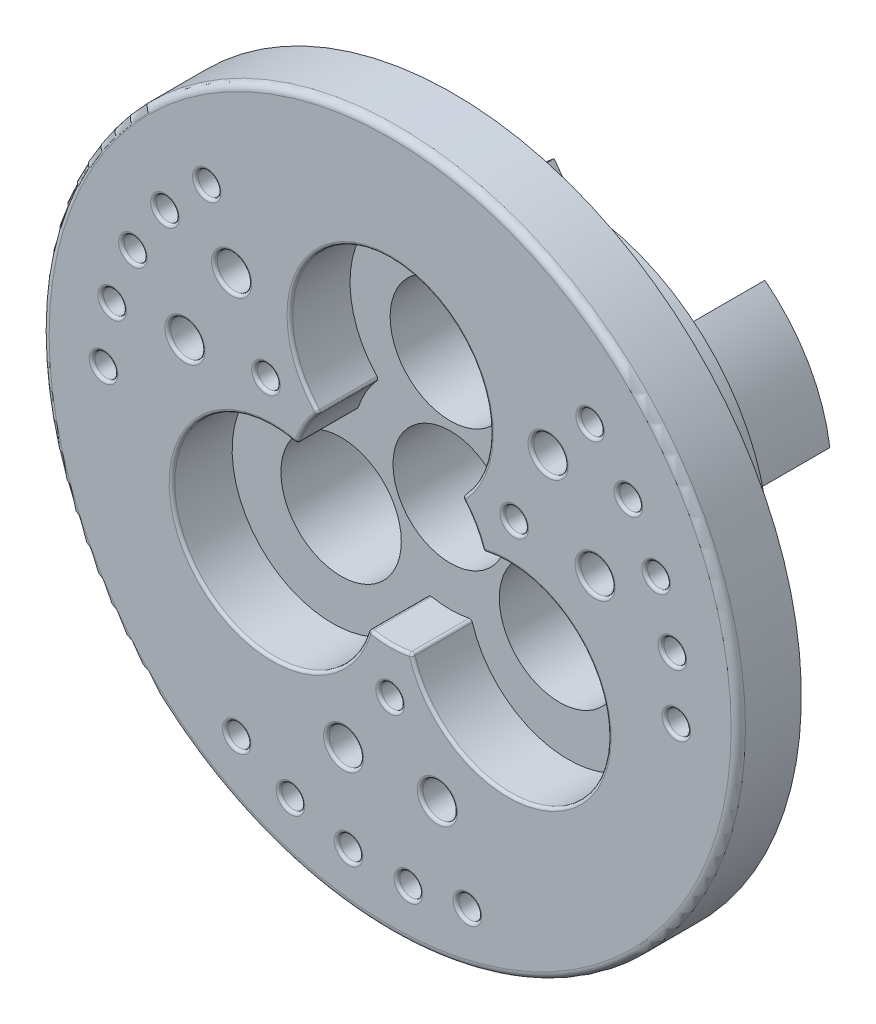
SolidWorks part; units mm, degrees
ref_plane "Plan de face" through (0, 0, 0) normal (0, 0, 1) x (1, 0, 0)
ref_plane "Plan de dessus" through (0, 0, 0) normal (0, 1, 0) x (1, 0, 0)
ref_plane "Plan de droite" through (0, 0, 0) normal (1, 0, 0) x (0, 0, -1)
sketch "Esquisse1" plane through (0, 0, 0) normal (1, 0, 0) x (0, 0, -1)
  line L0 (0, 20) -> (0, 70)
  line L1 (0, 70) -> (-40, 70)
  line L2 (-40, 70) -> (-40, 121.5)
  line L3 (-40, 121.5) -> (-62, 121.5)
  line L4 (-62, 121.5) -> (-62, 20)
  line L5 (-62, 20) -> (0, 20)
  line L6 (0, 0) -> (-218.9749, 0) construction
  dimension "D1" = 20
  dimension "D2" = 121.5
  dimension "D3" = 70
  dimension "D4" = 62
  dimension "D5" = 40
revolve "Révolution1" add sketch "Esquisse1" angle 360 about L6
sketch "Esquisse3" plane through (0, 0, 0) normal (0, 0, -1) x (-1, 0, 0)
  line L0 (0, 0) -> (0, 114.8369) construction
  line L1 (0, 0) -> (130.9393, 0) construction
  line L2 (0, 0) -> (103.8356, 59.9495) construction
  line L3 (59.4433, 8.1546) -> (27.5844, 4.8061)
  line L4 (17.9544, 21.4858) -> (36.7837, 47.4021)
  line L5 (9.63, -26.2919) -> (22.6595, -55.5567)
  line L6 (-22.6595, -55.5567) -> (-9.63, -26.2919)
  line L7 (-27.5844, 4.8061) -> (-59.4433, 8.1546)
  line L8 (-36.7837, 47.4021) -> (-17.9544, 21.4858)
  line L9 (0, 0) -> (27.5844, 4.8061) construction
  line L10 (0, 0) -> (0, 44) construction
  circle A0 centre (0, 44) radius 21
  arc A3 (27.5844, 4.8061) -> (17.9544, 21.4858) centre (0, 0) ccw
  arc A4 (59.4433, 8.1546) -> (36.7837, 47.4021) centre (0, 0) ccw
  arc A5 (-22.6595, -55.5567) -> (22.6595, -55.5567) centre (0, 0) ccw
  arc A6 (-9.63, -26.2919) -> (9.63, -26.2919) centre (0, 0) ccw
  arc A7 (-36.7837, 47.4021) -> (-59.4433, 8.1546) centre (0, 0) ccw
  arc A8 (-17.9544, 21.4858) -> (-27.5844, 4.8061) centre (0, 0) ccw
  circle A9 centre (38.1051, -22) radius 21
  circle A10 centre (-38.1051, -22) radius 21
  dimension "D2" = 42
  dimension "D4" = 3
  dimension "D1" = 30
  dimension "D3" = 44
  dimension "D5" = 28
  dimension "D6" = 24
  dimension "D7" = 24
  dimension "D9" = 44
  dimension "D8" = 3
extrude "Enlèv. mat.-Extru.1" cut sketch "Esquisse3" against normal offset from surface 20 and the other way through all contours A0 | A10 | A9 region at (0, 44, 0) region at (-38.1051, -22, 0) region at (38.1051, -22, 0) up to face at (-20, 0, 62)
extrude "Boss.-Extru.1" add sketch "Esquisse3<3>" along normal blind 32 contours A8 L8 A7 L7 | L3 A4 L4 A3 | A6 L6 A5 L5 region at (-39.0329, 22.5357, 0) region at (0, -45.0713, 0) region at (39.0329, 22.5357, 0)
sketch "Esquisse3<3>" plane through (0, 0, 0) normal (0, 0, -1) x (-1, 0, 0) same geometry as "Esquisse3"
sketch "Esquisse5" plane through (0, 0, 62) normal (0, 0, 1) x (1, 0, 0)
  line L0 (0, 0) -> (0, 47.5) construction
  circle A0 centre (0, 0) radius 47.5 construction
  arc A1 (25.0182, 23.0237) -> (-25.0182, 23.0237) centre (0, 47.5) ccw
  arc A2 (7.43, -33.1782) -> (32.4482, 10.1545) centre (41.1362, -23.75) ccw
  arc A3 (-32.4482, 10.1545) -> (-7.43, -33.1782) centre (-41.1362, -23.75) ccw
  arc A7 (-7.43, -33.1782) -> (7.43, -33.1782) centre (0, 0) ccw
  arc A8 (-25.0182, 23.0237) -> (-32.4482, 10.1545) centre (0, 0) ccw
  arc A9 (32.4482, 10.1545) -> (25.0182, 23.0237) centre (0, 0) ccw
  dimension "D1" = 95
  dimension "D2" = 70
  dimension "D4" = 68
  dimension "D3" = 3
extrude "Enlèv. mat.-Extru.2" cut sketch "Esquisse5" against normal blind 21
fillet "Congé1" radius 2.5 1 edges at (-121.5, 0, 62)
fillet "Congé2" radius 1 12 edges at (-7.43, -33.1782, 51.5) (7.43, -33.1782, 51.5) (32.4482, 10.1545, 51.5) (25.0182, 23.0237, 51.5) (-25.0182, 23.0237, 51.5) (-32.4482, 10.1545, 51.5) (-29.4449, 17, 62) (0, 82.5, 62) (29.4449, 17, 62) (71.4471, -41.25, 62) (0, -34, 62) (-71.4471, -41.25, 62)
sketch "Esquisse6" plane through (0, 0, -32) normal (0, 0, -1) x (-1, 0, 0)
  line L1 (0, 0) -> (-43.3013, 25) construction
  line L2 (-36.7837, 47.4021) -> (-17.9544, 21.4858) construction
  line L3 (-27.5776, 23.1404) -> (0, 0) construction
  line L4 (-36.7837, 47.4021) -> (-17.9544, 21.4858) construction
  line L5 (-33.8289, 12.3127) -> (0, 0) construction
  line L6 (-27.5844, 4.8061) -> (-59.4433, 8.1546) construction
  line L7 (0, 0) -> (-27.5776, 23.1404) construction
  circle A0 centre (-43.3013, 25) radius 6
  circle A1 centre (-33.8289, 12.3127) radius 4
  circle A2 centre (-27.5776, 23.1404) radius 4
  circle A3 centre (0, 0) radius 36 construction
  circle A4 centre (0, 0) radius 50 construction
  circle A5 centre (33.8289, 12.3127) radius 4
  circle A6 centre (27.5776, 23.1404) radius 4
  circle A7 centre (43.3013, 25) radius 6
  circle A8 centre (-6.2513, -35.4531) radius 4
  circle A9 centre (6.2513, -35.4531) radius 4
  circle A10 centre (0, -50) radius 6
  dimension "D1" = 12
  dimension "D2" = 8
  dimension "D3" = 8
  dimension "D5" = 72
  dimension "D6" = 100
  dimension "D4" = 14
  dimension "D7" = 24
  dimension "D8" = 14
  dimension "D10" = 36
  dimension "D9" = 3
hole_wizard "Trous de centrage Ø8.0mm1" positions "Esquisse7" profile "Esquisse8" hole size "Ø8.0" standard "ISO"
sketch "Esquisse7" plane through (0, 0, -32) normal (0, 0, -1) x (-1, 0, 0)
  point P0 (-27.5776, 23.1404)
  point P3 (-33.8289, 12.3127)
  point P7 (33.8289, 12.3127)
  point P10 (27.5776, 23.1404)
  point P13 (6.2513, -35.4531)
  point P16 (-6.2513, -35.4531)
sketch "Esquisse8" plane through (27.5776, 23.1404, -32) normal (1, 0, 0) x (0, 1, 0)
  line L0 (0, 0) -> (0, 24.4034)
  line L1 (0, 24.4034) -> (4, 22)
  line L2 (4, 22) -> (4, 0)
  line L5 (4, 0) -> (0, 0)
  line L10 (0, 24.4034) -> (-4, 22) construction
  line L11 (0, -6.35) -> (0, 107.95) construction
  dimension "Diamètre du perçage" = 8
  dimension "Profondeur du perçage" = 22
  dimension "Angle de pointe" = 118
hole_wizard "Dégagement M121" positions "Esquisse3D1" profile "Esquisse9" hole size "M12" standard "ISO"
sketch3d "Esquisse3D1"
  point P0 (43.3013, 25, -32)
  point P3 (0, -50, -32)
  point P6 (-43.3013, 25, -32)
sketch "Esquisse9" plane through (43.3013, 25, -32) normal (1, 0, 0) x (0, 1, 0)
  line L0 (0, 0) -> (0, 31.9056)
  line L1 (0, 31.9056) -> (6.5, 28)
  line L2 (6.5, 28) -> (6.5, 0)
  line L5 (6.5, 0) -> (0, 0)
  line L10 (0, 31.9056) -> (-6.5, 28) construction
  line L11 (0, -6.35) -> (0, 107.95) construction
  dimension "Diamètre du perçage" = 13
  dimension "Profondeur du perçage" = 28
  dimension "Angle de pointe" = 118
sketch "Esquisse10" plane through (0, 0, 62) normal (0, 0, 1) x (1, 0, 0)
  line L0 (-0.0806, -4.0148) -> (-100.0174, 0) construction
  line L1 (-55.2958, 50.6693) -> (0, 0) construction
  line L2 (0, 0) -> (-100.0174, 0) construction
  line L3 (0, 0) -> (-71.6069, 22.3038) construction
  line L4 (0, 0) -> (-55.2958, 50.6693) construction
  circle A0 centre (0, 0) radius 100.0174 construction
  circle A1 centre (-100.0174, 0) radius 4
  circle A5 centre (-96.9988, 20.6903) radius 4
  circle A6 centre (-89.7444, 40.3008) radius 4
  circle A7 centre (-78.5713, 57.9746) radius 4
  circle A8 centre (-63.9678, 72.9391) radius 4
  circle A9 centre (-46.5721, 84.5404) radius 4 [skipped]
  circle A10 centre (-27.1444, 92.2713) radius 4 [skipped]
  circle A11 centre (-6.534, 95.7941) radius 4 [skipped]
  circle A12 centre (14.3584, 94.9548) radius 4 [skipped]
  circle A13 centre (34.6199, 89.79) radius 4 [skipped]
  circle A14 centre (53.3647, 80.5255) radius 4 [skipped]
  circle A15 centre (69.7737, 67.5662) radius 4
  circle A16 centre (83.1298, 51.4785) radius 4
  circle A17 centre (92.8491, 32.9654) radius 4
  circle A18 centre (98.507, 12.8361) radius 4
  circle A19 centre (99.8561, -8.0296) radius 4
  circle A20 centre (96.8376, -28.7199) radius 4 [skipped]
  circle A21 centre (89.5832, -48.3305) radius 4 [skipped]
  circle A22 centre (78.4101, -66.0042) radius 4 [skipped]
  circle A23 centre (63.8065, -80.9687) radius 4 [skipped]
  circle A24 centre (46.4108, -92.57) radius 4 [skipped]
  circle A25 centre (26.9832, -100.301) radius 4
  circle A26 centre (6.3728, -103.8238) radius 4
  circle A27 centre (-14.5197, -102.9844) radius 4
  circle A28 centre (-34.7811, -97.8197) radius 4
  circle A29 centre (-53.5259, -88.5552) radius 4
  circle A30 centre (-69.9349, -75.5959) radius 4 [skipped]
  circle A31 centre (-83.291, -59.5081) radius 4 [skipped]
  circle A32 centre (-93.0104, -40.995) radius 4 [skipped]
  circle A33 centre (-98.6682, -20.8658) radius 4 [skipped]
  circle A34 centre (0, -50) radius 4
  circle A35 centre (43.3013, 25) radius 4
  circle A36 centre (-43.3013, 25) radius 4
  circle A37 centre (0, 0) radius 75 construction
  circle A38 centre (-71.6069, 22.3038) radius 6
  circle A39 centre (-55.2958, 50.6693) radius 6
  circle A40 centre (71.5288, 22.5529) radius 6
  circle A41 centre (55.1191, 50.8615) radius 6
  circle A42 centre (-16.233, -73.2222) radius 6
  circle A43 centre (16.4878, -73.1652) radius 6
  dimension "D1" = 8
  dimension "D2" = 30
  dimension "D4" = 12
  dimension "D5" = 12
  dimension "D6" = 8
  dimension "D7" = 8
  dimension "D8" = 8
  dimension "D3" = 100.0174
  dimension "D9" = 15
  dimension "D10" = 42.5
  dimension "D12" = 75
  dimension "D11" = 3
extrude "Enlèv. mat.-Extru.3" cut sketch "Esquisse10" against normal up to surface (21 mm away) up to face at (20, 0, 41)
fillet "Congé3" radius 1 24 edges at (-49.5259, -88.5552, 62) (-30.7811, -97.8197, 62) (-10.5197, -102.9844, 62) (10.3728, -103.8238, 62) (30.9832, -100.301, 62) (-10.233, -73.2222, 62) (4, -50, 62) (22.4878, -73.1652, 62) (103.8561, -8.0296, 62) (96.8491, 32.9654, 62) (102.507, 12.8361, 62) (77.5288, 22.5529, 62) (73.7737, 67.5662, 62) (87.1298, 51.4785, 62) (61.1191, 50.8615, 62) (47.3013, 25, 62) (-39.3013, 25, 62) (-49.2958, 50.6693, 62) (-65.6069, 22.3038, 62) (-96.0174, 0, 62) (-92.9988, 20.6903, 62) (-85.7444, 40.3008, 62) (-74.5713, 57.9746, 62) (-59.9678, 72.9391, 62)
